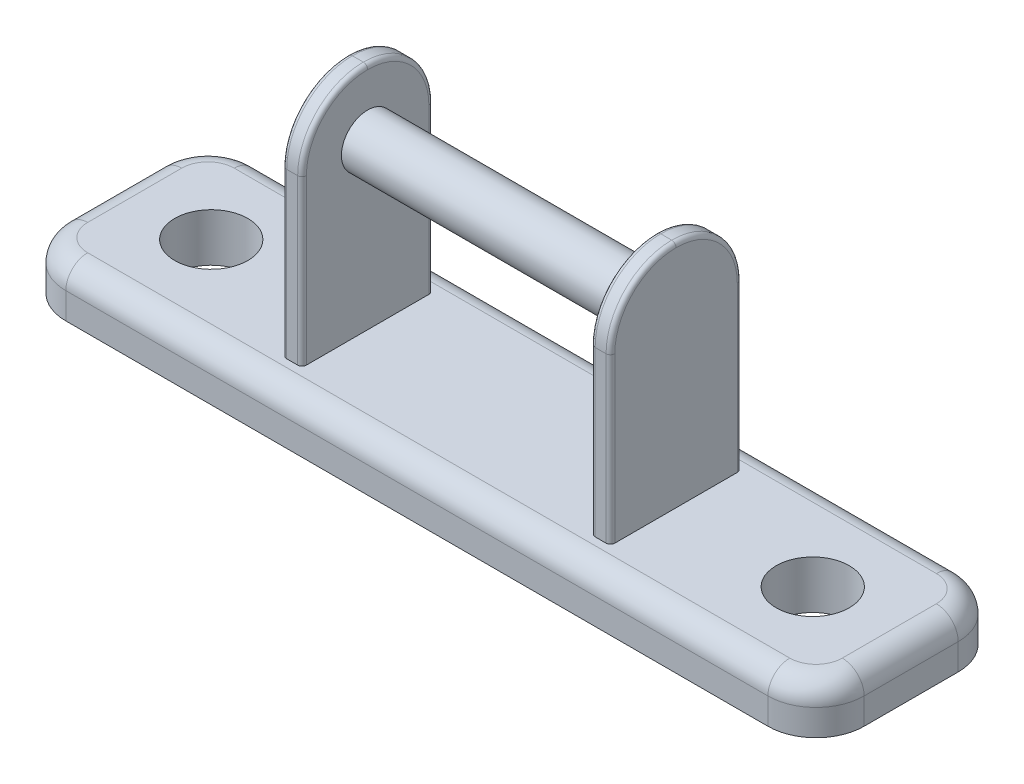
SolidWorks part; units mm, degrees
ref_plane "Front Plane" through (0, 0, 0) normal (0, 0, 1) x (1, 0, 0)
ref_plane "Top Plane" through (0, 0, 0) normal (0, 1, 0) x (1, 0, 0)
ref_plane "Right Plane" through (0, 0, 0) normal (1, 0, 0) x (0, 0, -1)
sketch "Sketch1" plane through (0, 0, 0) normal (0, 1, 0) x (1, 0, 0)
  line L0 (-1000, 0) -> (49000, 0) construction
  line L1 (23.1775, -5.5245) -> (-23.1775, -5.5245)
  line L2 (23.1775, -5.5245) -> (23.1775, 5.5245)
  line L3 (23.1775, 5.5245) -> (-23.1775, 5.5245)
  line L4 (-23.1775, -5.5245) -> (-23.1775, 5.5245)
  line L5 (23.1775, -5.5245) -> (-23.1775, 5.5245) construction
  line L6 (23.1775, 5.5245) -> (-23.1775, -5.5245) construction
  line L7 (0, -1000) -> (0, 49000) construction
  circle A0 centre (-17.4625, 0) radius 2.1209
  circle A1 centre (17.4625, 0) radius 2.1209
  point P0 (0, 0)
  dimension "D3" = 4.2418
  dimension "D1" = 46.355
  dimension "D2" = 11.049
  dimension "D4" = 34.925
extrude "Boss-Extrude1" add sketch "Sketch1" against normal blind 2.794
sketch "Sketch2" plane through (0, 0, 0) normal (0, 1, 0) x (1, 0, 0)
  line L0 (0, -1000) -> (0, 49000) construction
  line L1 (-1000, 0) -> (49000, 0) construction
  line L2 (-8.382, 3.81) -> (-9.525, -3.81) construction
  line L3 (8.382, -3.81) -> (9.525, -3.81)
  line L4 (8.382, -3.81) -> (8.382, 3.81)
  line L5 (8.382, 3.81) -> (9.525, 3.81)
  line L6 (9.525, -3.81) -> (9.525, 3.81)
  line L7 (8.382, -3.81) -> (9.525, 3.81) construction
  line L8 (8.382, 3.81) -> (9.525, -3.81) construction
  line L9 (-8.382, -3.81) -> (-9.525, 3.81) construction
  line L10 (1000, 0) -> (-49000, 0) construction
  line L11 (-9.525, -3.81) -> (-9.525, 3.81)
  line L12 (-8.382, 3.81) -> (-9.525, 3.81)
  line L13 (-8.382, -3.81) -> (-8.382, 3.81)
  line L14 (-8.382, -3.81) -> (-9.525, -3.81)
  point P4 (8.9535, 0)
  point P16 (-8.9535, 0)
  dimension "D1" = 1.143
  dimension "D2" = 7.62
  dimension "D3" = 16.764
extrude "Boss-Extrude2" add sketch "Sketch2" along normal blind 13.335
fillet "Fillet1" radius 3.81 4 edges at (-8.9535, 13.335, -3.81) (-8.9535, 13.335, 3.81) (8.9535, 13.335, -3.81) (8.9535, 13.335, 3.81)
sketch "Sketch3" plane through (-8.382, 0, 0) normal (1, 0, 0) x (0, 0, -1)
  circle A0 centre (0, 9.525) radius 1.524
  dimension "D1" = 3.048
extrude "Boss-Extrude3" add sketch "Sketch3" along normal up to surface (16.764 mm away) up to face at (8.382, 6.7926, 0)
fillet "Fillet2" radius 2.794 4 edges at (23.1775, -1.397, 5.5245) (23.1775, -1.397, -5.5245) (-23.1775, -1.397, -5.5245) (-23.1775, -1.397, 5.5245)
fillet "Fillet3" radius 1.27 8 edges at (-22.3592, 0, 4.7062) (-23.1775, 0, 0) (-22.3592, 0, -4.7062) (0, 0, -5.5245) (22.3592, 0, -4.7062) (23.1775, 0, 0) (22.3592, 0, 4.7062) (0, 0, 5.5245)
fillet "Fillet4" radius 0.254 16 edges at (-8.382, 4.7625, -3.81) (-8.382, 4.7625, 3.81) (-8.382, 12.2191, 2.6941) (8.382, 4.7625, 3.81) (8.382, 4.7625, -3.81) (8.382, 12.2191, -2.6941) (-9.525, 4.7625, 3.81) (-9.525, 12.2191, 2.6941) (-9.525, 4.7625, -3.81) (9.525, 4.7625, -3.81) (9.525, 4.7625, 3.81) (9.525, 12.2191, 2.6941) (-8.382, 12.2191, -2.6941) (8.382, 12.2191, 2.6941) (-9.525, 12.2191, -2.6941) (9.525, 12.2191, -2.6941)
